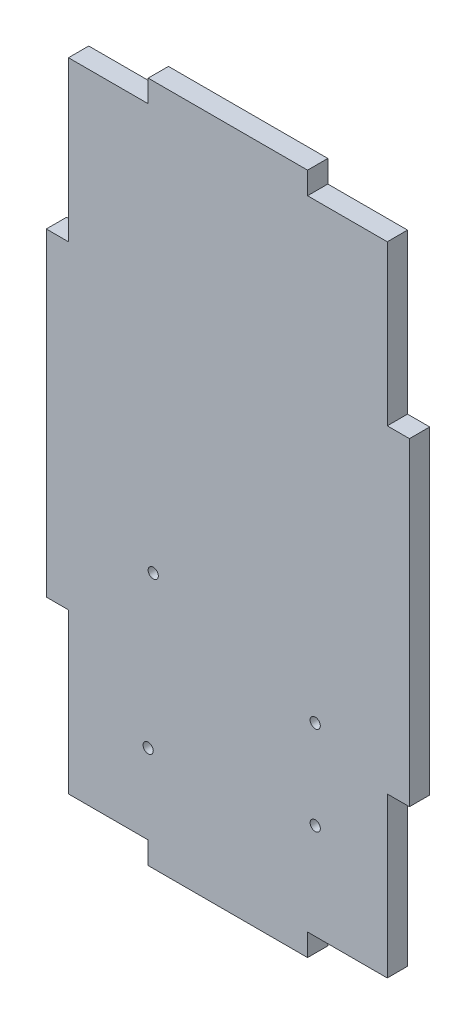
SolidWorks part; units mm, degrees
ref_plane "Front Plane" through (0, 0, 0) normal (0, 0, 1) x (1, 0, 0)
ref_plane "Top Plane" through (0, 0, 0) normal (0, 1, 0) x (1, 0, 0)
ref_plane "Right Plane" through (0, 0, 0) normal (1, 0, 0) x (0, 0, -1)
sketch "Sketch1" plane through (0, 0, 0) normal (0, 0, 1) x (1, 0, 0)
  line L1 (-50, 100) -> (50, 100)
  line L2 (-50, 100) -> (-50, -100)
  line L3 (-50, -100) -> (50, -100)
  line L4 (50, 100) -> (50, -100)
  line L5 (-50, 100) -> (50, -100) construction
  line L6 (-50, -100) -> (50, 100) construction
  point P0 (0, 0)
  dimension "D1" = 200
  dimension "D2" = 100
extrude "Boss-Extrude1" add sketch "Sketch1" along normal blind 6.36
sketch "Sketch2" [suppressed] plane through (0, 0, 3.36) normal (0, 0, 1) x (1, 0, 0)
  line L0 (50, 50) -> (-50, 50) construction
  line L1 (-25, 50) -> (25, 50)
  line L2 (-25, 50) -> (-25, 53.36)
  line L3 (-25, 53.36) -> (25, 53.36)
  line L4 (25, 50) -> (25, 53.36)
  line L5 (0, 0) -> (0, 53.36) construction
  line L6 (0, 0) -> (50, 0) construction
  line L7 (50, -50) -> (50, 50) construction
  dimension "D1" = 6.36
  dimension "D2" = 50
sketch "Sketch8" plane through (0, 0, 0) normal (0, 0, -1) x (-1, 0, 0)
  line L0 (0, 0) -> (0, 100) construction
  line L1 (-50, 100) -> (50, 100) construction
  line L2 (0, 0) -> (50, 0) construction
  line L3 (50, 100) -> (50, -100) construction
  line L5 (-25, 100) -> (25, 100)
  line L6 (-25, 100) -> (-25, 106.96)
  line L7 (-25, 106.96) -> (25, 106.96)
  line L8 (25, 100) -> (25, 106.96)
  dimension "D2" = 6.96
  dimension "D1" = 50
extrude "Boss-Extrude4" add sketch "Sketch8" against normal blind 6.36
mirror "Mirror4" about plane through (0, 0, 0) normal (0, 1, 0) of "Boss-Extrude4"
sketch "Sketch9" plane through (0, 0, 0) normal (0, 0, -1) x (-1, 0, 0)
  line L0 (0, 0) -> (50, 0) construction
  line L1 (50, 100) -> (50, -100) construction
  line L3 (50, 50) -> (56.96, 50)
  line L4 (50, 50) -> (50, -50)
  line L5 (50, -50) -> (56.96, -50)
  line L6 (56.96, 50) -> (56.96, -50)
  dimension "D1" = 100
  dimension "D2" = 6.96
extrude "Boss-Extrude5" add sketch "Sketch9" against normal blind 6.36
mirror "Mirror5" about plane through (0, 0, 0) normal (1, 0, 0) of "Boss-Extrude5"
sketch "Sketch10" plane through (0, 0, 6.36) normal (0, 0, 1) x (1, 0, 0)
  line L0 (0, 0) -> (0, 50) construction
  line L1 (50, 100) -> (25, 100) construction
  line L3 (-22.1665, 100) -> (22.1665, 100)
  line L4 (-22.1665, 100) -> (-22.1665, 90.4825)
  line L5 (-22.1665, 90.4825) -> (22.1665, 90.4825)
  line L6 (22.1665, 100) -> (22.1665, 90.4825)
  dimension "D1" = 9.5175
  dimension "D2" = 44.3329
extrude "Cut-Extrude1" [suppressed] cut sketch "Sketch10" against normal through all and the other way through all
mirror "Mirror6" [suppressed] about plane through (0, 0, 0) normal (0, 1, 0)
sketch "Sketch11" plane through (0, 0, 6.36) normal (0, 0, 1) x (1, 0, 0)
  line L0 (0, 0) -> (50, 0) construction
  line L1 (50, -100) -> (50, -50) construction
  line L3 (50, 18.3322) -> (46.2005, 18.3322)
  line L4 (50, 18.3322) -> (50, -18.3322)
  line L5 (50, -18.3322) -> (46.2005, -18.3322)
  line L6 (46.2005, 18.3322) -> (46.2005, -18.3322)
  dimension "D1" = 3.7995
  dimension "D2" = 36.6643
extrude "Cut-Extrude2" [suppressed] cut sketch "Sketch11" against normal through all and the other way through all
mirror "Mirror7" [suppressed] about plane through (0, 0, 0) normal (1, 0, 0)
sketch "Sketch12" plane through (0, 0, 6.36) normal (0, 0, 1) x (1, 0, 0)
  line L0 (-50, -50) -> (-50, -100) construction
  line L1 (-50, -100) -> (-25, -100) construction
  line L2 (-25, -75) -> (-25, -26.7) construction
  line L3 (27.4, -42) -> (27.4, -69.9) construction
  circle A0 centre (-25, -75) radius 1.6
  circle A1 centre (-23.4, -26.7) radius 1.6
  circle A2 centre (27.4, -69.9) radius 1.6
  circle A3 centre (27.4, -42) radius 1.6
  dimension "D1" = 3.2
  dimension "D2" = 25
  dimension "D3" = 25
  dimension "D5" = 48.3
  dimension "D7" = 5.1
  dimension "D9" = 50.8
  dimension "D10" = 27.9
extrude "arduino holes" cut sketch "Sketch12" against normal through all and the other way through all
sketch "Sketch13" plane through (0, 0, 6.36) normal (0, 0, 1) x (1, 0, 0)
  line L0 (25.9457, -65) -> (-18.2265, -65) construction
  line L1 (50, -100) -> (50, -50) construction
  line L2 (25, -100) -> (50, -100) construction
  circle A0 centre (25.9457, -65) radius 2
  circle A1 centre (-16.3351, -43.7788) radius 2
  circle A2 centre (-16.3351, -86.2212) radius 2
  dimension "D1" = 4
  dimension "D2" = 42.4424
  dimension "D3" = 42.2808
  dimension "D4" = 24.0543
  dimension "D5" = 35
extrude "battery holes" [suppressed] cut sketch "Sketch13" against normal blind 10
sketch "Sketch14" [suppressed] plane through (0, 0, 0) normal (0, 0, -1) x (-1, 0, 0)
  line L6 (33.2, -18.84) -> (45.2, -18.84)
  line L8 (45.2, -29.34) -> (33.2, -29.34)
  line L9 (45.2, -18.84) -> (45.2, -29.34)
  line L10 (33.2, -29.34) -> (33.2, -18.84)
  line L52 (50, -44.24) -> (50, -50)
  line L53 (50, -50) -> (100, -50)
  line L54 (100, -50) -> (100, -25)
  line L55 (100, -25) -> (106.96, -25)
  line L56 (106.96, -25) -> (106.96, 25)
  line L57 (106.96, 25) -> (100, 25)
  line L58 (100, 25) -> (100, 50)
  line L59 (100, 50) -> (50, 50)
  line L60 (50, 50) -> (50, 44.24)
  line L61 (50, 44.24) -> (-50, 44.24)
  line L62 (-50, 44.24) -> (-50, 50)
  line L63 (-50, 50) -> (-100, 50)
  line L64 (-100, 50) -> (-100, 25)
  line L65 (-100, 25) -> (-106.96, 25)
  line L66 (-106.96, 25) -> (-106.96, -25)
  line L67 (-106.96, -25) -> (-100, -25)
  line L68 (-100, -25) -> (-100, -50)
  line L69 (-100, -50) -> (-50, -50)
  line L70 (-50, -50) -> (-50, -44.24)
  line L71 (-50, -44.24) -> (50, -44.24)
  point P0 (-100, 50)
extrude "Cut-Extrude6" [suppressed] cut sketch "Sketch14" against normal through all contours L10 L8 L9 L6
sketch "Sketch15" [suppressed] plane through (0, 0, 0) normal (0, 0, -1) x (-1, 0, 0)
  line L0 (50.6, 25) -> (50.6, -25) construction
  line L1 (27.42, 19.24) -> (30.6, 19.24)
  line L2 (27.42, 19.24) -> (27.42, 6.74)
  line L3 (27.42, 6.74) -> (30.6, 6.74)
  line L4 (30.6, 19.24) -> (30.6, 6.74)
  line L5 (24.7, 44.24) -> (-24.7, 44.24) construction
  dimension "D1" = 12.5
  dimension "D2" = 3.18
  dimension "D3" = 20
  dimension "D4" = 25
extrude "Cut-Extrude7" [suppressed] cut sketch "Sketch15" against normal blind 10
sketch "Sketch16" plane through (0, 0, 0) normal (0, 0, -1) x (-1, 0, 0)
  line L0 (-25, -100) -> (-50, -100) construction
  line L1 (-50, -100) -> (-50, -50) construction
  line L2 (50, -50) -> (50, -100) construction
  circle A0 centre (-10, -80) radius 4
  circle A1 centre (-25, -80) radius 3.35
  circle A2 centre (0, -30) radius 3.35
  dimension "D1" = 8
  dimension "D2" = 6.7
  dimension "D3" = 20
  dimension "D4" = 20
  dimension "D5" = 25
  dimension "D6" = 40
  dimension "D7" = 6.7
  dimension "D8" = 70
  dimension "D9" = 50
extrude "Cut-Extrude8" [suppressed] cut sketch "Sketch16" against normal blind 10
equation "\"Sheet Thickness\"= 6.36mm"
equation "\"Height\"= 100mm"
equation "\"Length\"= 200mm"
equation "\"Width\"= 100mm"
equation "\"D1@Boss-Extrude1\"=\"Sheet Thickness\""
equation "\"D1@Sketch2\"=\"Sheet Thickness\""
equation "\"D2@Sketch2\"=\"Height\"/2"
equation "\"Kerf\"= .60mm"
equation "\"D2@Sketch9\"=\"Sheet Thickness\"+\"Kerf\""
equation "\"D1@Sketch9\"     = \"Length\"/2"
equation "\"D2@Sketch8\"=\"Sheet Thickness\"+\"Kerf\""
equation "\"D1@Sketch10\"=\"Sheet Thickness\"-\"Kerf\""
equation "\"D2@Sketch10\"      = \"Width\"/2"
equation "\"D1@Sketch11\"=\"Sheet Thickness\"-\"Kerf\""
equation "\"D2@Sketch11\"=\"Height\"/2"
